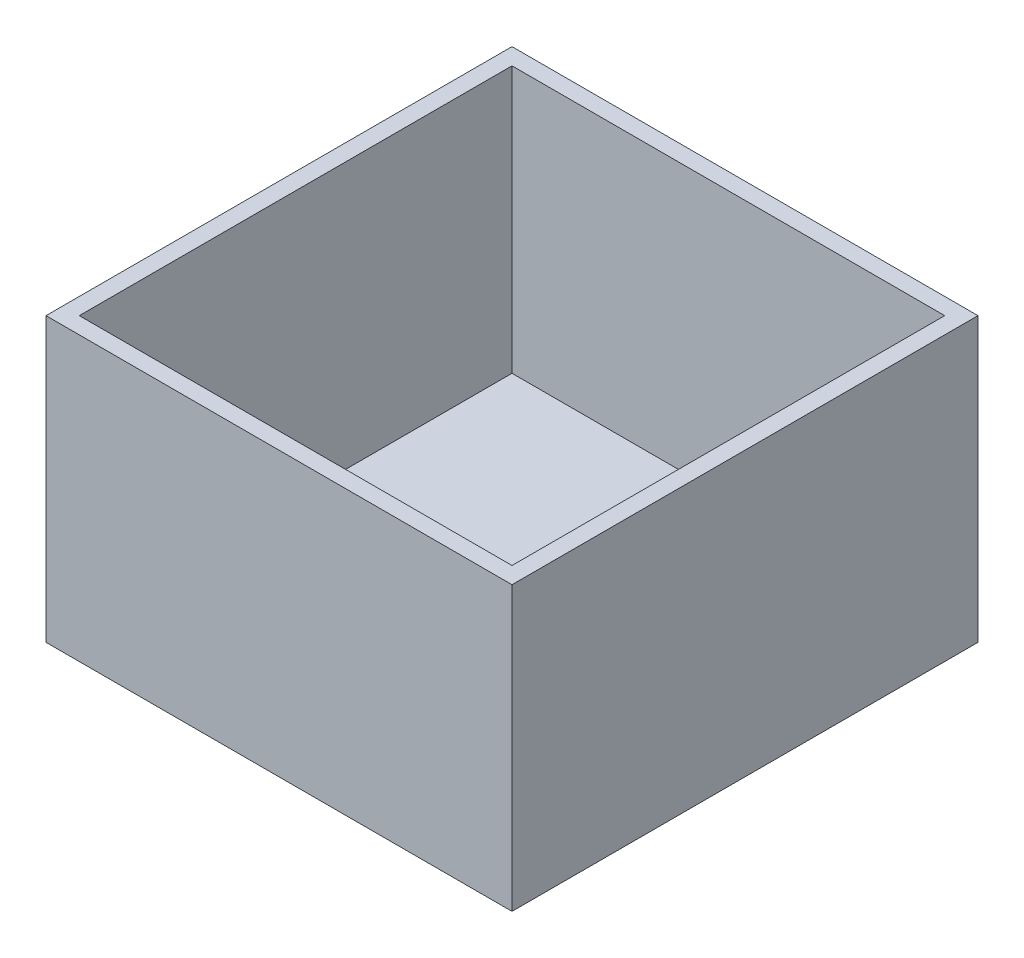
SolidWorks part; units mm, degrees
ref_plane "Front Plane" through (0, 0, 0) normal (0, 0, 1) x (1, 0, 0)
ref_plane "Top Plane" through (0, 0, 0) normal (0, 1, 0) x (1, 0, 0)
ref_plane "Right Plane" through (0, 0, 0) normal (1, 0, 0) x (0, 0, -1)
sketch "Sketch1" plane through (0, 0, 0) normal (0, 1, 0) x (1, 0, 0)
  line L1 (0, 0) -> (56, 0)
  line L2 (0, 0) -> (0, 56)
  line L3 (0, 56) -> (56, 56)
  line L4 (56, 0) -> (56, 56)
  dimension "D1" = 56
  dimension "D2" = 56
extrude "Boss-Extrude1" add sketch "Sketch1" along normal blind 2
sketch "Sketch2" plane through (0, 2, 0) normal (0, 1, 0) x (1, 0, 0)
  line L5 (0, 56) -> (56, 56)
  line L6 (0, 56) -> (0, 0)
  line L7 (0, 0) -> (56, 0)
  line L8 (2, 54) -> (2, 2)
  line L9 (2, 2) -> (54, 2)
  line L10 (54, 2) -> (54, 54)
  line L11 (54, 54) -> (2, 54)
  line L12 (2, 54) -> (2, 2)
  line L13 (2, 2) -> (54, 2)
  line L14 (54, 2) -> (54, 54)
  line L15 (54, 54) -> (2, 54)
  line L16 (56, 56) -> (56, 0)
  dimension "D1" = 2
extrude "Boss-Extrude2" add sketch "Sketch2" along normal blind 32
sketch "Sketch3" plane through (0, 34, 0) normal (0, 1, 0) x (1, 0, 0)
  line L0 (56, 0) -> (56, 56) construction
  line L1 (0, 0) -> (56, 0)
  line L2 (0, 0) -> (0, 28)
  line L3 (0, 28) -> (56, 28)
  line L4 (56, 0) -> (56, 28)
extrude "Cut-Extrude1" [suppressed] cut sketch "Sketch3" against normal blind 10
